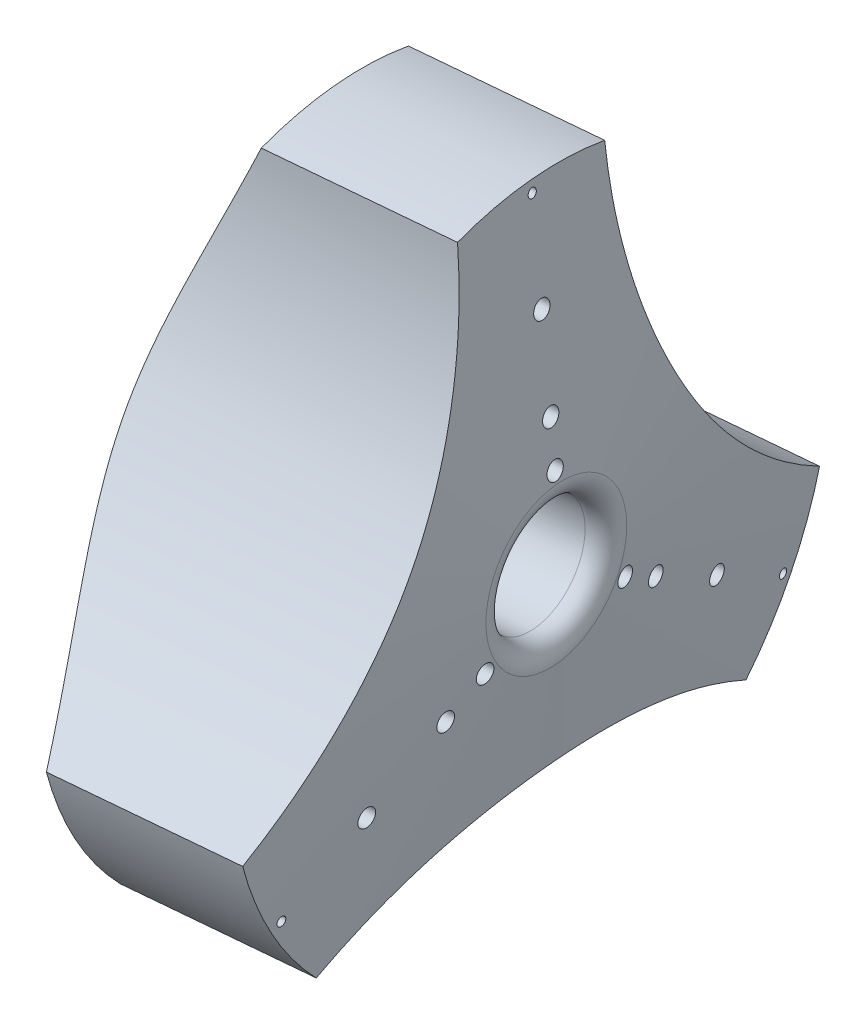
SolidWorks part; units mm, degrees
material "ABS"
ref_plane "前视基准面" through (0, 0, 0) normal (0, 0, 1) x (1, 0, 0)
ref_plane "上视基准面" through (0, 0, 0) normal (0, 1, 0) x (1, 0, 0)
ref_plane "右视基准面" through (0, 0, 0) normal (1, 0, 0) x (0, 0, -1)
other "Configuration Table"
sketch "草图1" plane through (0, 0, 0) normal (0, 1, 0) x (1, 0, 0)
  line L0 (0, 0) -> (50000, 0) construction
  line L1 (0, 0) -> (43301.2702, 25000) construction
  line L2 (0, 0) -> (25000, 43301.2702) construction
  line L3 (0, 0) -> (0, 50000) construction
  line L4 (0, 0) -> (-24999.9997, 43301.2704) construction
  line L5 (0, 0) -> (-43301.2702, 25000) construction
  line L10 (0, 73.354) -> (-40.226, 69.6734)
  line L11 (-40.226, 69.6734) -> (-81.0426, 140.3699)
  line L12 (-81.0426, 140.3699) -> (0, 147.7852)
  line L13 (18.3541, 0) -> (55.6014, 0)
  line L14 (-293.1662, 0) -> (-96.7748, 0)
  line L15 (0, 147.7852) -> (0, 73.354)
  line L16 (-38.4595, 144.2662) -> (-37.5483, 134.3078) construction
  line L17 (-37.5483, 134.3078) -> (0, 137.7434)
  line L18 (-37.5483, 134.3078) -> (-75.5359, 130.832)
  spline S0 degree 4 poles (0, -13.9122) (0.4288, -13.9878) (1.2926, -14.1039) (2.6002, -14.1722) (4.3419, -14.0551) (6.0103, -13.7444) (7.773, -13.21) (9.593, -12.4079) (11.2813, -11.3833) (13.0108, -9.9981) (14.579, -8.3636) (15.8921, -6.573) (16.7894, -4.9125) (17.3145, -3.6768) (17.5885, -2.9241) (17.7037, -2.5872) (17.8123, -2.2481) (17.9142, -1.9072) (18.0095, -1.5637) (18.0983, -1.2182) (18.1691, -0.9197) (18.2269, -0.6559) (18.2831, -0.3813) (18.3354, -0.109) (18.3711, 0.0925) (18.4139, 0.3573) (18.4465, 0.5746) (18.4705, 0.7447) (18.4976, 0.9523) (18.5267, 1.1986) (18.5568, 1.4891) (18.5855, 1.8227) (18.6082, 2.1561) (18.625, 2.4897) (18.6415, 2.9908) (18.6444, 3.7428) (18.6, 4.7901) (18.4544, 6.1268) (18.1183, 7.9493) (17.5241, 9.9881) (16.6153, 12.1533) (15.4328, 14.2054) (14.026, 16.1623) (12.2754, 18.1012) (10.149, 19.9482) (7.4457, 21.6944) (4.4784, 23.0742) (1.2971, 24.0486) (-2.1866, 24.6091) (-5.9175, 24.6633) (-9.7618, 24.1432) (-13.6227, 23.0043) (-17.2722, 21.3076) (-20.6387, 19.103) (-24.4169, 15.784) (-28.1648, 11.0227) (-31.3154, 4.4225) (-32.9538, -4.4321) (-32.0375, -14.0948) (-28.1424, -23.7302) (-21.3685, -32.1908) (-12.5515, -38.4704) (-2.4126, -42.2287) (8.3331, -43.3372) (19.0234, -41.8455) (29.7828, -37.6697) (40.3424, -30.2375) (49.4452, -19.1893) (55.5551, -4.7492) (57.3753, 11.4017) (54.7581, 27.4228) (48.0949, 42.2071) (37.9905, 54.8719) (25.1812, 64.7711) (10.4646, 71.4886) (-5.3559, 74.8179) (-21.5135, 74.7355) (-37.3086, 71.3698) (-52.1281, 64.9701) (-65.4574, 55.8769) (-76.8843, 44.4931) (-86.0992, 31.2617) (-92.9569, 16.4959) (-98.2612, -3.1071) (-99.3529, -27.5578) (-93.1302, -55.5464) (-77.0987, -83.8533) (-53.8578, -106.5556) (-25.4602, -122.2617) (5.9606, -130.2467) (38.3519, -130.3634) (69.8553, -122.9377) (98.8778, -108.6588) (124.1284, -88.4759) (144.6286, -63.5047) (159.7045, -34.9474) (168.9656, -4.026) (172.2746, 28.0696) (169.7138, 60.222) (161.5485, 91.4149) (148.1919, 120.752) (130.171, 147.4681) (108.095, 170.9338) (82.6276, 190.6548) (54.4619, 206.2675) (24.299, 217.5313) (-7.1689, 224.319) (-39.2739, 226.6058) (-71.3835, 224.4579) (-98.969, 218.8252) (-121.9134, 211.4493) (-140.4165, 203.6877) (-154.7919, 196.546) (-168.6874, 188.5108) (-182.0538, 179.6235) (-196.4446, 168.7156) (-208.5171, 158.129) (-219.9251, 146.8372) (-231.9749, 133.3951) (-241.9655, 120.8263) (-251.0758, 107.6061) (-258.3626, 95.6046) (-263.2354, 86.8412) (-266.9323, 79.7223) (-270.4259, 72.5015) (-273.7143, 65.185) (-276.4108, 58.7049) (-278.5921, 53.0984) (-280.3227, 48.3937) (-281.6549, 44.6108) (-282.9345, 40.8105) (-284.1616, 36.9917) (-285.3356, 33.1583) (-286.4574, 29.3057) (-287.5253, 25.4437) (-288.5419, 21.5581) (-289.5026, 17.675) (-290.3013, 14.2402) (-290.9454, 11.3302) (-291.4717, 8.8337) (-291.8579, 6.9561) (-292.2757, 4.8213) (-292.5987, 3.1456) (-293.0036, 0.9209) (-293.2168, -0.28) (-293.5445, -2.179) (-293.8363, -3.9367) (-294.1828, -6.1075) (-294.5484, -8.5333) (-294.8987, -10.9902) (-295.2261, -13.4346) (-295.5347, -15.89) (-295.8945, -18.9572) (-296.2863, -22.6451) (-296.6843, -26.9519) (-297.0589, -31.8818) (-297.3529, -36.8165) (-297.5669, -41.7558) (-297.7007, -46.6976) (-297.7547, -51.6411) (-297.729, -56.5848) (-297.624, -61.5274) (-297.4397, -66.4677) (-296.9135, -76.3411) (-295.6855, -89.8862) (-293.2164, -107.0261) (-288.82, -127.5848) (-284.8275, -141.8776) (-281.7816, -151.2859) (-280.1641, -155.9573) knots 0 0 0 0 0 0.000986 0.001973 0.002959 0.003945 0.004822 0.006138 0.007453 0.008403 0.009829 0.011255 0.012465 0.012667 0.012868 0.01307 0.013272 0.013473 0.013675 0.013876 0.014078 0.014179 0.01428 0.014481 0.01467 0.014765 0.01486 0.014954 0.015049 0.015238 0.015427 0.015617 0.015806 0.015995 0.016184 0.016752 0.017509 0.018368 0.019228 0.020946 0.022309 0.023673 0.024581 0.026398 0.028215 0.030031 0.031848 0.033788 0.035728 0.037999 0.04027 0.042541 0.044813 0.047084 0.049355 0.053897 0.05844 0.063467 0.069524 0.07558 0.081637 0.087693 0.093749 0.099806 0.105862 0.111919 0.119671 0.128756 0.137841 0.146925 0.15601 0.165095 0.174179 0.183264 0.192349 0.201434 0.210519 0.219603 0.228688 0.237773 0.246858 0.255942 0.265027 0.274475 0.292645 0.310814 0.328984 0.347153 0.365322 0.383492 0.401661 0.41983 0.438 0.456169 0.474339 0.492508 0.510678 0.528847 0.547017 0.565186 0.583356 0.601525 0.619695 0.637864 0.656034 0.674203 0.692373 0.710542 0.728712 0.746881 0.755966 0.765051 0.774136 0.78322 0.792305 0.80139 0.815017 0.81956 0.828644 0.842271 0.851356 0.855899 0.860441 0.864984 0.869526 0.874068 0.878611 0.880882 0.883153 0.885424 0.887695 0.889967 0.892238 0.894509 0.89678 0.899052 0.901323 0.903594 0.90473 0.905865 0.907001 0.908137 0.909272 0.910408 0.911108 0.911808 0.913208 0.914607 0.916007 0.917407 0.918807 0.920207 0.921607 0.924407 0.927206 0.930006 0.932806 0.935606 0.938405 0.941205 0.944005 0.946805 0.949604 0.952404 0.966403 0.977602 0.988801 1 1 1 1 1 construction
  spline S1 degree 4 poles (18.3541, 0) (18.3671, 0.0737) (18.3859, 0.1846) (18.4139, 0.3573) (18.4465, 0.5746) (18.4705, 0.7447) (18.4976, 0.9523) (18.5267, 1.1986) (18.5568, 1.4891) (18.5855, 1.8227) (18.6082, 2.1561) (18.625, 2.4897) (18.6415, 2.9908) (18.6444, 3.7428) (18.6, 4.7901) (18.4544, 6.1268) (18.1183, 7.9493) (17.5241, 9.9881) (16.6153, 12.1533) (15.4328, 14.2054) (14.026, 16.1623) (12.2754, 18.1012) (10.149, 19.9482) (7.4457, 21.6944) (4.4784, 23.0742) (1.2971, 24.0486) (-2.1866, 24.6091) (-5.9175, 24.6633) (-9.7618, 24.1432) (-13.6227, 23.0043) (-17.2722, 21.3076) (-20.6387, 19.103) (-24.4169, 15.784) (-28.1648, 11.0227) (-31.3154, 4.4225) (-32.9538, -4.4321) (-32.0375, -14.0948) (-28.1424, -23.7302) (-21.3685, -32.1908) (-12.5515, -38.4704) (-2.4126, -42.2287) (8.3331, -43.3372) (19.0234, -41.8455) (29.7828, -37.6697) (40.3424, -30.2375) (49.4452, -19.1893) (55.5551, -4.7492) (57.3753, 11.4017) (54.7581, 27.4228) (48.0949, 42.2071) (37.9905, 54.8719) (25.1812, 64.7711) (10.4646, 71.4886) (-5.3559, 74.8179) (-21.5135, 74.7355) (-37.3086, 71.3698) (-52.1281, 64.9701) (-65.4574, 55.8769) (-76.8843, 44.4931) (-86.0992, 31.2617) (-92.9569, 16.4959) (-98.2612, -3.1071) (-99.3529, -27.5578) (-93.1302, -55.5464) (-77.0987, -83.8533) (-53.8578, -106.5556) (-25.4602, -122.2617) (5.9606, -130.2467) (38.3519, -130.3634) (69.8553, -122.9377) (98.8778, -108.6588) (124.1284, -88.4759) (144.6286, -63.5047) (159.7045, -34.9474) (168.9656, -4.026) (172.2746, 28.0696) (169.7138, 60.222) (161.5485, 91.4149) (148.1919, 120.752) (130.171, 147.4681) (108.095, 170.9338) (82.6276, 190.6548) (54.4619, 206.2675) (24.299, 217.5313) (-7.1689, 224.319) (-39.2739, 226.6058) (-71.3835, 224.4579) (-98.969, 218.8252) (-121.9134, 211.4493) (-140.4165, 203.6877) (-154.7919, 196.546) (-168.6874, 188.5108) (-182.0538, 179.6235) (-196.4446, 168.7156) (-208.5171, 158.129) (-219.9251, 146.8372) (-231.9749, 133.3951) (-241.9655, 120.8263) (-251.0758, 107.6061) (-258.3626, 95.6046) (-263.2354, 86.8412) (-266.9323, 79.7223) (-270.4259, 72.5015) (-273.7143, 65.185) (-276.4108, 58.7049) (-278.5921, 53.0984) (-280.3227, 48.3937) (-281.6549, 44.6108) (-282.9345, 40.8105) (-284.1616, 36.9917) (-285.3356, 33.1583) (-286.4574, 29.3057) (-287.5253, 25.4437) (-288.5419, 21.5581) (-289.5026, 17.675) (-290.3013, 14.2402) (-290.9454, 11.3302) (-291.4717, 8.8337) (-291.8579, 6.9561) (-292.2757, 4.8213) (-292.5987, 3.1456) (-292.9346, 1.3001) (-293.0882, 0.4423) (-293.1662, 0) knots 0.014481 0.014481 0.014481 0.014481 0.014481 0.01467 0.014765 0.01486 0.014954 0.015049 0.015238 0.015427 0.015617 0.015806 0.015995 0.016184 0.016752 0.017509 0.018368 0.019228 0.020946 0.022309 0.023673 0.024581 0.026398 0.028215 0.030031 0.031848 0.033788 0.035728 0.037999 0.04027 0.042541 0.044813 0.047084 0.049355 0.053897 0.05844 0.063467 0.069524 0.07558 0.081637 0.087693 0.093749 0.099806 0.105862 0.111919 0.119671 0.128756 0.137841 0.146925 0.15601 0.165095 0.174179 0.183264 0.192349 0.201434 0.210519 0.219603 0.228688 0.237773 0.246858 0.255942 0.265027 0.274475 0.292645 0.310814 0.328984 0.347153 0.365322 0.383492 0.401661 0.41983 0.438 0.456169 0.474339 0.492508 0.510678 0.528847 0.547017 0.565186 0.583356 0.601525 0.619695 0.637864 0.656034 0.674203 0.692373 0.710542 0.728712 0.746881 0.755966 0.765051 0.774136 0.78322 0.792305 0.80139 0.815017 0.81956 0.828644 0.842271 0.851356 0.855899 0.860441 0.864984 0.869526 0.874068 0.878611 0.880882 0.883153 0.885424 0.887695 0.889967 0.892238 0.894509 0.89678 0.899052 0.901323 0.903594 0.90473 0.905865 0.907001 0.908137 0.909272 0.910408 0.910408 0.910408 0.910408 0.910408
  spline S2 degree 4 poles (18.4059, -25.3335) (19.107, -24.9916) (20.4868, -24.262) (22.5206, -23.0115) (25.0808, -21.0705) (27.4721, -18.8597) (29.6657, -16.3937) (31.6129, -13.729) (33.0896, -11.2475) (34.1864, -9.0304) (34.9057, -7.3212) (35.3416, -6.1645) (35.6757, -5.1903) (35.9253, -4.405) (36.1573, -3.6144) (36.3716, -2.8185) (36.5434, -2.119) (36.6687, -1.5643) (36.7535, -1.1663) (36.8052, -0.9135) (36.8466, -0.7052) (36.8982, -0.4372) (36.9567, -0.1213) (37.0035, 0.1434) (37.0749, 0.5721) (37.1371, 0.9717) (37.2058, 1.4486) (37.2819, 2.0322) (37.3587, 2.7131) (37.4305, 3.4924) (37.4863, 4.2735) (37.526, 5.0553) (37.5559, 6.0336) (37.5599, 7.208) (37.5186, 8.5778) (37.4086, 10.1401) (37.1505, 12.4751) (36.6019, 15.5617) (35.6708, 18.9675) (34.2579, 22.6243) (32.7042, 25.7897) (31.1185, 28.4933) (29.3394, 31.0737) (27.3788, 33.5189) (25.249, 35.8182) (22.9627, 37.9618) (20.5329, 39.9412) (17.3329, 42.201) (13.6843, 44.3112) (9.5794, 46.1791) (4.9351, 47.7364) (0.5493, 48.7741) (-5.1759, 49.5807) (-12.2448, 49.6897) (-20.4322, 48.5637) (-29.4144, 45.6531) (-37.7662, 41.2547) (-45.2725, 35.5359) (-51.7593, 28.6855) (-57.0931, 20.9063) (-61.1792, 12.4073) (-63.9591, 3.398) (-65.4072, -5.9168) (-65.5277, -15.3413) (-64.3508, -24.6913) (-61.9292, -33.7971) (-58.3342, -42.5053) (-53.6526, -50.6795) (-47.9834, -58.201) (-41.4348, -64.9693) (-34.1214, -70.9013) (-26.1617, -75.9314) (-17.6761, -80.0102) (-8.7848, -83.1042) (0.3937, -85.1942) (9.7443, -86.2746) (19.1561, -86.352) (28.5237, -85.4444) (37.7479, -83.5791) (48.7429, -80.1706) (61.3712, -74.3882) (74.9241, -65.3639) (88.2878, -52.3646) (99.2288, -36.9666) (107.3051, -19.8977) (112.3659, -1.711) (114.3597, 17.056) (113.3221, 35.8954) (109.3632, 54.3391) (102.6547, 71.9655) (93.418, 88.4046) (81.9129, 103.34) (68.427, 116.5097) (53.2659, 127.7056) (36.7454, 136.7708) (19.1839, 143.5977) (0.8963, 148.1237) (-17.8115, 150.3284) (-36.6464, 150.2287) (-55.332, 147.8751) (-73.6111, 143.3474) (-91.2474, 136.7503) (-108.0274, 128.21) (-121.7938, 119.1626) (-132.8352, 110.3812) (-141.486, 102.4316) (-148.0599, 95.7143) (-154.2723, 88.6613) (-160.1094, 81.2949) (-165.5592, 73.6375) (-171.8736, 63.7306) (-176.9453, 54.4461) (-180.9636, 45.947) (-183.8818, 38.8929) (-185.1615, 35.6104) (-186.1831, 32.858) (-186.9734, 30.6462) (-187.7366, 28.425) (-188.4727, 26.1945) (-189.1816, 23.9554) (-189.8633, 21.7077) (-190.5178, 19.4522) (-191.145, 17.1885) (-191.7448, 14.9181) (-192.3174, 12.6396) (-192.8623, 10.3561) (-193.3803, 8.0634) (-193.8088, 6.0566) (-194.131, 4.4692) (-194.3554, 3.3245) (-194.4957, 2.592) (-194.6042, 2.0172) (-194.7054, 1.4732) (-194.8177, 0.857) (-194.937, 0.1911) (-195.0219, -0.2913) (-195.1581, -1.0772) (-195.2723, -1.7539) (-195.4156, -2.6211) (-195.5862, -3.6835) (-195.7746, -4.9054) (-195.9819, -6.3152) (-196.2274, -8.0725) (-196.5025, -10.1875) (-196.7938, -12.6566) (-197.0869, -15.4841) (-197.3398, -18.3147) (-197.5528, -21.1491) (-197.7258, -23.9859) (-197.8589, -26.8251) (-197.9522, -29.6657) (-198.0191, -33.2178) (-198.0202, -37.4813) (-197.8411, -45.2961) (-197.0568, -56.6437) (-195.3598, -69.3345) (-193.0445, -80.4735) (-191.2905, -87.36) (-190.5403, -90.1013) knots 0 0 0 0 0 0.00302 0.006041 0.00923 0.01242 0.01561 0.0188 0.02199 0.023585 0.02518 0.025978 0.026776 0.027573 0.028371 0.029168 0.029966 0.030365 0.030564 0.030763 0.030963 0.031162 0.031561 0.03194 0.032319 0.032698 0.033077 0.033835 0.034592 0.03535 0.036108 0.036866 0.037624 0.039139 0.040655 0.042171 0.043686 0.048233 0.05278 0.055812 0.058843 0.061874 0.064906 0.067937 0.070969 0.074 0.077031 0.080063 0.086126 0.090292 0.094458 0.099005 0.103552 0.112646 0.12174 0.130835 0.139929 0.149023 0.158117 0.167211 0.176305 0.185399 0.194493 0.203588 0.212682 0.221776 0.23087 0.239964 0.249059 0.258153 0.267247 0.276341 0.285435 0.294529 0.303624 0.312718 0.321812 0.330906 0.34 0.349094 0.36631 0.384498 0.402687 0.420875 0.439063 0.457252 0.47544 0.493628 0.511817 0.530005 0.548193 0.566382 0.58457 0.602758 0.620947 0.639135 0.657323 0.675512 0.6937 0.711888 0.730077 0.748265 0.766453 0.784642 0.793736 0.80283 0.811924 0.821018 0.830112 0.839207 0.848301 0.866489 0.871036 0.875583 0.877857 0.88013 0.882404 0.884678 0.886951 0.889225 0.891498 0.893772 0.896045 0.898319 0.900592 0.902866 0.90514 0.907413 0.90855 0.909118 0.909687 0.910255 0.910823 0.911392 0.91196 0.912648 0.913336 0.914024 0.914711 0.916087 0.917463 0.918838 0.920214 0.922965 0.925716 0.928468 0.931219 0.93397 0.936721 0.939473 0.942224 0.944975 0.950478 0.95598 0.972488 0.988995 1 1 1 1 1 construction
  spline S3 degree 4 poles (36.9778, 0) (36.9927, 0.0848) (37.022, 0.2547) (37.0749, 0.5721) (37.1371, 0.9717) (37.2058, 1.4486) (37.2819, 2.0322) (37.3587, 2.7131) (37.4305, 3.4924) (37.4863, 4.2735) (37.526, 5.0553) (37.5559, 6.0336) (37.5599, 7.208) (37.5186, 8.5778) (37.4086, 10.1401) (37.1505, 12.4751) (36.6019, 15.5617) (35.6708, 18.9675) (34.2579, 22.6243) (32.7042, 25.7897) (31.1185, 28.4933) (29.3394, 31.0737) (27.3788, 33.5189) (25.249, 35.8182) (22.9627, 37.9618) (20.5329, 39.9412) (17.3329, 42.201) (13.6843, 44.3112) (9.5794, 46.1791) (4.9351, 47.7364) (0.5493, 48.7741) (-5.1759, 49.5807) (-12.2448, 49.6897) (-20.4322, 48.5637) (-29.4144, 45.6531) (-37.7662, 41.2547) (-45.2725, 35.5359) (-51.7593, 28.6855) (-57.0931, 20.9063) (-61.1792, 12.4073) (-63.9591, 3.398) (-65.4072, -5.9168) (-65.5277, -15.3413) (-64.3508, -24.6913) (-61.9292, -33.7971) (-58.3342, -42.5053) (-53.6526, -50.6795) (-47.9834, -58.201) (-41.4348, -64.9693) (-34.1214, -70.9013) (-26.1617, -75.9314) (-17.6761, -80.0102) (-8.7848, -83.1042) (0.3937, -85.1942) (9.7443, -86.2746) (19.1561, -86.352) (28.5237, -85.4444) (37.7479, -83.5791) (48.7429, -80.1706) (61.3712, -74.3882) (74.9241, -65.3639) (88.2878, -52.3646) (99.2288, -36.9666) (107.3051, -19.8977) (112.3659, -1.711) (114.3597, 17.056) (113.3221, 35.8954) (109.3632, 54.3391) (102.6547, 71.9655) (93.418, 88.4046) (81.9129, 103.34) (68.427, 116.5097) (53.2659, 127.7056) (36.7454, 136.7708) (19.1839, 143.5977) (0.8963, 148.1237) (-17.8115, 150.3284) (-36.6464, 150.2287) (-55.332, 147.8751) (-73.6111, 143.3474) (-91.2474, 136.7503) (-108.0274, 128.21) (-121.7938, 119.1626) (-132.8352, 110.3812) (-141.486, 102.4316) (-148.0599, 95.7143) (-154.2723, 88.6613) (-160.1094, 81.2949) (-165.5592, 73.6375) (-171.8736, 63.7306) (-176.9453, 54.4461) (-180.9636, 45.947) (-183.8818, 38.8929) (-185.1615, 35.6104) (-186.1831, 32.858) (-186.9734, 30.6462) (-187.7366, 28.425) (-188.4727, 26.1945) (-189.1816, 23.9554) (-189.8633, 21.7077) (-190.5178, 19.4522) (-191.145, 17.1885) (-191.7448, 14.9181) (-192.3174, 12.6396) (-192.8623, 10.3561) (-193.3803, 8.0634) (-193.8088, 6.0566) (-194.131, 4.4692) (-194.3554, 3.3245) (-194.4957, 2.592) (-194.6042, 2.0172) (-194.7054, 1.4732) (-194.8177, 0.857) (-194.9027, 0.3825) (-194.948, 0.1273) (-194.9705, 0) knots 0.031561 0.031561 0.031561 0.031561 0.031561 0.03194 0.032319 0.032698 0.033077 0.033835 0.034592 0.03535 0.036108 0.036866 0.037624 0.039139 0.040655 0.042171 0.043686 0.048233 0.05278 0.055812 0.058843 0.061874 0.064906 0.067937 0.070969 0.074 0.077031 0.080063 0.086126 0.090292 0.094458 0.099005 0.103552 0.112646 0.12174 0.130835 0.139929 0.149023 0.158117 0.167211 0.176305 0.185399 0.194493 0.203588 0.212682 0.221776 0.23087 0.239964 0.249059 0.258153 0.267247 0.276341 0.285435 0.294529 0.303624 0.312718 0.321812 0.330906 0.34 0.349094 0.36631 0.384498 0.402687 0.420875 0.439063 0.457252 0.47544 0.493628 0.511817 0.530005 0.548193 0.566382 0.58457 0.602758 0.620947 0.639135 0.657323 0.675512 0.6937 0.711888 0.730077 0.748265 0.766453 0.784642 0.793736 0.80283 0.811924 0.821018 0.830112 0.839207 0.848301 0.866489 0.871036 0.875583 0.877857 0.88013 0.882404 0.884678 0.886951 0.889225 0.891498 0.893772 0.896045 0.898319 0.900592 0.902866 0.90514 0.907413 0.90855 0.909118 0.909687 0.910255 0.910823 0.911392 0.91196 0.91196 0.91196 0.91196 0.91196
  dimension "D1" = 10
revolve "旋转1" add sketch "草图1" angle 360 about L12 region at (-30.0285, 0, -106.7505) region at (-20.1464, 0, -72.58)
ref_plane "基准面1" through (12.4986, 0, -1.1436) normal (0.9958, 0, -0.0911) x (-0.0911, 0, -0.9958)
sketch "草图2" plane through (12.4986, 0, -1.1436) normal (0.9958, 0, -0.0911) x (-0.0911, 0, -0.9958)
  line L0 (147.1704, 0) -> (147.1704, 20) construction
  line L1 (147.1704, 20) -> (147.1704, 30) construction
  line L2 (147.1704, 30) -> (147.1704, 50) construction
  line L3 (147.1704, 74.1215) -> (147.1704, 71.6215)
  line L4 (147.1704, 0) -> (18.9986, 74) construction
  circle A0 centre (147.1704, 0) radius 74.1215 construction
  circle A1 centre (147.1704, 20) radius 2
  circle A2 centre (147.1704, 30) radius 2
  circle A3 centre (147.1704, 50) radius 2
  circle A4 centre (147.1704, 71.6215) radius 1
  circle A5 centre (18.9986, 74) radius 110
  circle A6 centre (275.3422, 74) radius 110
  circle A7 centre (209.1965, -35.8108) radius 1
  circle A8 centre (190.4717, -25) radius 2
  circle A9 centre (173.1512, -15) radius 2
  circle A10 centre (164.4909, -10) radius 2
  circle A11 centre (147.1704, -148) radius 110
  circle A12 centre (85.1443, -35.8108) radius 1
  circle A13 centre (103.8691, -25) radius 2
  circle A14 centre (121.1896, -15) radius 2
  circle A15 centre (129.8499, -10) radius 2
  circle A16 centre (147.1704, 0) radius 12.5
  dimension "D5" = 4
  dimension "D6" = 4
  dimension "D7" = 4
  dimension "D8" = 2
  dimension "D10" = 220
  dimension "D12" = 25
  dimension "D1" = 20
  dimension "D2" = 10
  dimension "D3" = 20
  dimension "D4" = 2.5
  dimension "D9" = 60
  dimension "D11" = 3
extrude "切除-拉伸1" cut sketch "草图2" against normal blind 105 contours A5 | A6 | A11 | A16 | A4 | A3 | A2 | A1 | A15 | A14 | A13 | A12 | A10 | A9 | A8 | A7 region at (10.7675, 74, -20.0632) region at (-12.5898, 74, -275.3404) region at (-0.9112, -148, -147.7018) region at (-0.9112, 0, -147.7018)
fillet "圆角1" radius 4.5 1 edges at (0, 0, -135.2329)
shell "抽壳1" thickness 2
ref_plane "基准面2" through (-13.2275, 0, -144.5665) normal (-0.0911, 0, -0.9958) x (-0.9958, 0, 0.0911)
ref_plane "基准面3" through (-13.4097, 0, -146.5582) normal (-0.0911, 0, -0.9958) x (-0.9958, 0, 0.0911)
sketch "草图3" plane through (-13.4097, 0, -146.5582) normal (-0.0911, 0, -0.9958) x (-0.9958, 0, 0.0911)
  line L0 (-10.3803, 16.4663) -> (58.6704, 16.4663)
  line L1 (-9.9423, 23.6974) -> (55.0197, 23.6974)
  line L2 (-9.9423, 23.6974) -> (-9.9423, 26.3669)
  line L3 (-9.9423, 26.3669) -> (55.0197, 26.3669)
  line L4 (55.0197, 23.6974) -> (55.0197, 26.3669)
  line L5 (58.6704, 16.4663) -> (59.7822, 14.0368)
  line L6 (59.7822, 14.0368) -> (-10.1052, 14.0368)
  line L7 (-10.1052, 14.0368) -> (-10.9411, 15.8634)
  line L8 (-10.9411, 15.8634) -> (-10.3803, 16.4663)
  line L9 (-5.6491, 69.1937) -> (34.4329, 69.1937)
  line L10 (34.4329, 69.1937) -> (41.5986, 53.5353)
  line L11 (41.5986, 53.5353) -> (-7.0785, 53.5353)
  line L12 (-7.0785, 53.5353) -> (-5.6491, 69.1937)
  spline S0 degree 3 poles (-6.6838, 71.8542) (-7.0933, 67.2146) (-7.4897, 62.6235) (-8.2404, 53.5339) (-8.5953, 49.0354) (-9.0669, 42.3563) (-9.2137, 40.1413) (-9.412, 36.8361) (-9.4742, 35.7412) (-9.5892, 33.5715) (-9.6421, 32.4956) (-9.8811, 27.1606) (-9.988, 23.0341) (-9.9896, 15.0592) (-9.8842, 11.2108) (-9.6452, 6.5797) (-9.5921, 5.6612) (-9.4769, 3.8487) (-9.415, 2.9566) (-9.218, 0.3221) (-9.072, -1.3785) (-8.6021, -6.3172) (-8.2475, -9.3928) (-7.683, -13.683) (-7.4891, -15.059) (-7.0923, -17.7012) (-6.8892, -18.9692) (-6.6838, -20.1718) knots 0 0 0 0 0.125 0.125 0.25 0.25 0.3125 0.3125 0.34375 0.34375 0.375 0.375 0.5 0.5 0.625 0.625 0.65625 0.65625 0.6875 0.6875 0.75 0.75 0.875 0.875 0.9375 0.9375 1 1 1 1 construction
extrude "凸台-拉伸1" add sketch "草图3" along normal mid plane 1
ref_axis "基准轴1" through (-74.7323, 0, -140.9473) along (0.9958, 0, -0.0911)
pattern_circular "阵列(圆周)1" count 3 over 360 about axis through (-74.7323, 0, -140.9473) along (0.9958, 0, -0.0911) of "凸台-拉伸1"
